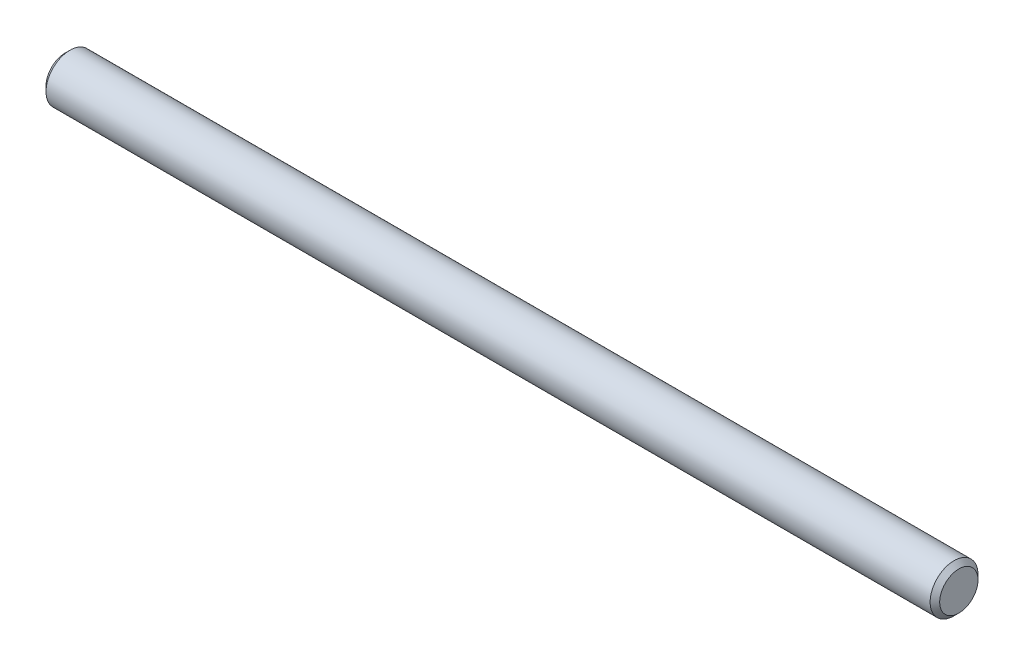
SolidWorks part; units mm, degrees
material "Plain Carbon Steel"
ref_plane "Front" through (0, 0, 0) normal (0, 0, 1) x (1, 0, 0)
ref_plane "Top" through (0, 0, 0) normal (0, 1, 0) x (1, 0, 0)
ref_plane "Right" through (0, 0, 0) normal (1, 0, 0) x (0, 0, -1)
sketch "Sketch1" plane through (0, 0, 0) normal (0, 0, 1) x (1, 0, 0)
  line L0 (-88.9, 0) -> (88.9, 0) construction
  line L1 (88.9, 4.7625) -> (88.9, -4.7625) construction
  line L2 (-88.9, 4.7625) -> (-88.9, -4.7625) construction
  dimension "Length" = 177.8
  dimension "Diameter" = 9.525
sketch "Sketch2" plane through (0, 0, 0) normal (1, 0, 0) x (0, 0, -1)
  circle A0 centre (0, 0) radius 4.7625
extrude "Extrude1" add sketch "Sketch2" against normal up to vertex (88.9 mm away) and the other way up to vertex (88.9 mm away) up to point (-88.9, 4.7625, 0) other way up to point (88.9, 4.7625, 0)
chamfer "Chamfer1" distance 0.9525 angle 45 2 edges at (88.9, 0, -4.7625) (-88.9, 0, -4.7625)
equation "\"D1@Chamfer1\" = \"Diameter@Sketch1\"*.1"
